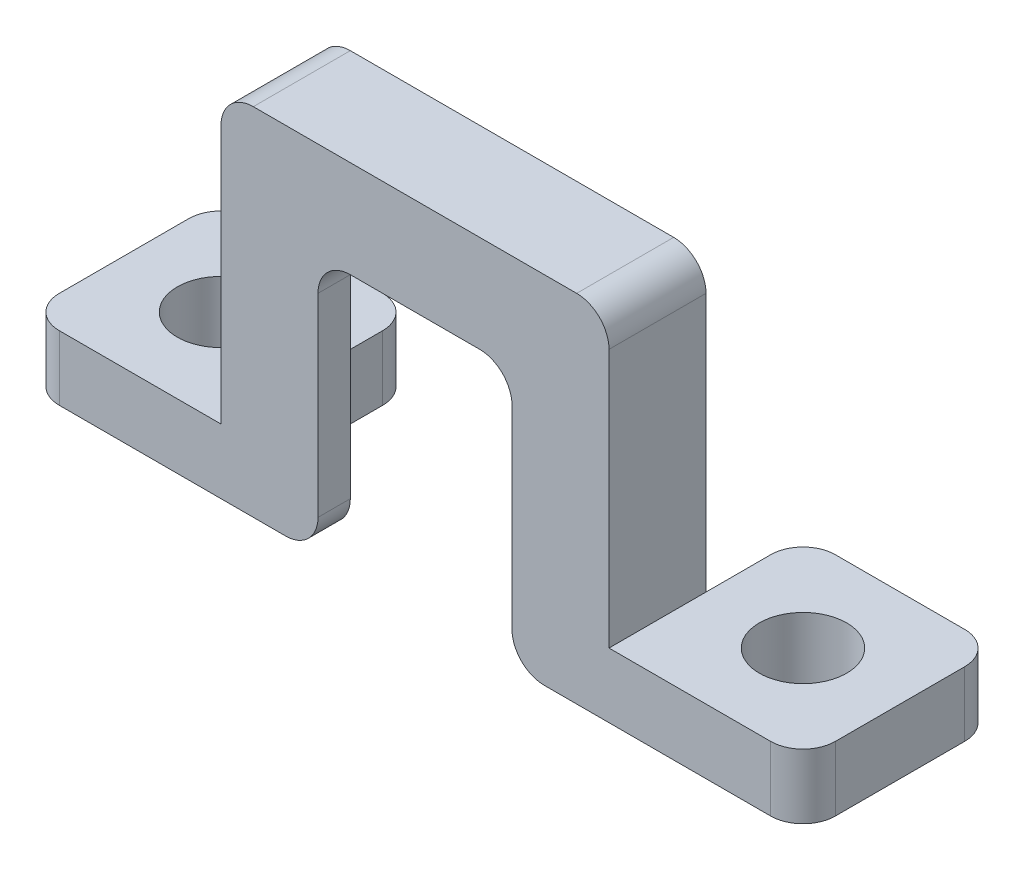
SolidWorks part; units mm, degrees
ref_plane "Front Plane" through (0, 0, 0) normal (0, 0, 1) x (1, 0, 0)
ref_plane "Top Plane" through (0, 0, 0) normal (0, 1, 0) x (1, 0, 0)
ref_plane "Right Plane" through (0, 0, 0) normal (1, 0, 0) x (0, 0, -1)
sketch "Sketch1" plane through (0, 0, 0) normal (0, 0, 1) x (1, 0, 0)
  line L0 (-2.54, 0) -> (-2.54, 27.94)
  line L1 (0, 0) -> (25.4, 0)
  line L2 (0, 0) -> (0, 25.4)
  line L3 (0, 25.4) -> (25.4, 25.4)
  line L4 (25.4, 0) -> (25.4, 25.4)
  line L5 (-2.54, 27.94) -> (27.94, 27.94)
  line L6 (27.94, 0) -> (27.94, 27.94)
  line L7 (-2.54, 0) -> (0, 0)
  line L8 (25.4, 0) -> (27.94, 0)
  line L9 (5.08, 0) -> (5.08, 20.32)
  line L10 (5.08, 20.32) -> (20.32, 20.32)
  line L11 (20.32, 0) -> (20.32, 20.32)
  dimension "D1" = 25.4
  dimension "D2" = 25.4
  dimension "D3" = 2.54
  dimension "D4" = 5.08
extrude "Boss-Extrude1" add sketch "Sketch1" along normal blind 2.54 contours L4 L8 L6 L5 L0 L7 L2 L3 | L11 L1 L4 L3 L2 L9 L10 region at (-2.1265, 13.97, 0) region at (0.3592, 12.7, 0)
extrude "Boss-Extrude2" add sketch "Sketch1<3>" against normal blind 5.08 contours L4 L8 L6 L5 L0 L7 L2 L3 region at (-2.1265, 13.97, 0)
sketch "Sketch1<3>" plane through (0, 0, 0) normal (0, 0, 1) x (1, 0, 0) same geometry as "Sketch1"
sketch "Sketch2" plane through (0, 0, 0) normal (0, -1, 0) x (1, 0, 0)
  line L0 (35.56, 2.54) -> (35.56, -12.7) construction
  line L1 (27.94, 2.54) -> (43.18, 2.54)
  line L2 (27.94, 2.54) -> (27.94, -12.7)
  line L3 (27.94, -12.7) -> (43.18, -12.7)
  line L4 (43.18, 2.54) -> (43.18, -12.7)
  line L5 (43.18, -5.08) -> (27.94, -5.08) construction
  circle A0 centre (35.56, -5.08) radius 3.429
  circle A1 centre (35.56, -5.08) radius 7.62 construction
  point P11 (35.56, -1.651)
  point P12 (38.989, -5.08)
  point P14 (0, 0)
  dimension "D3" = 6.858
  dimension "D1" = 15.24
extrude "Boss-Extrude3" add sketch "Sketch2" against normal blind 5.08
ref_plane "Plane1" through (12.7, 0, 0) normal (1, 0, 0) x (0, 0, -1)
mirror "Mirror1" about plane through (12.7, 0, 0) normal (1, 0, 0) of "Boss-Extrude3"
fillet "Fillet1" radius 2.54 12 edges at (20.32, 20.32, 1.27) (5.08, 20.32, 1.27) (5.08, 0, 1.27) (20.32, 0, 1.27) (-2.54, 27.94, -1.27) (27.94, 27.94, -1.27) (27.94, 2.54, -12.7) (43.18, 2.54, -12.7) (43.18, 2.54, 2.54) (-2.54, 2.54, -12.7) (-17.78, 2.54, -12.7) (-17.78, 2.54, 2.54)
